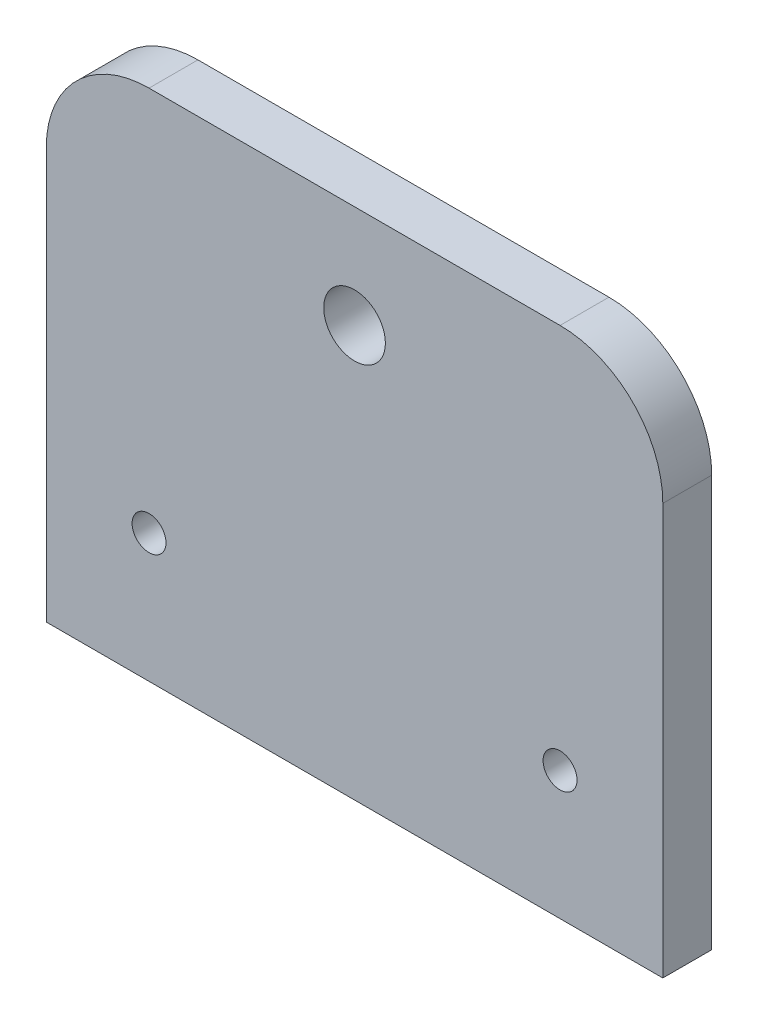
SolidWorks part; units mm, degrees
ref_plane "Front Plane" through (0, 0, 0) normal (0, 0, 1) x (1, 0, 0)
ref_plane "Top Plane" through (0, 0, 0) normal (0, 1, 0) x (1, 0, 0)
ref_plane "Right Plane" through (0, 0, 0) normal (1, 0, 0) x (0, 0, -1)
sketch "Sketch1" plane through (0, 0, 0) normal (0, 0, 1) x (1, 0, 0)
  line L1 (0, 0) -> (60, 0)
  line L2 (0, 0) -> (0, 50)
  line L3 (0, 50) -> (60, 50)
  line L4 (60, 0) -> (60, 50)
  dimension "D1" = 50
  dimension "D2" = 60
extrude "Boss-Extrude1" add sketch "Sketch1" along normal blind 4.76
sketch "Sketch2" plane through (0, 0, 4.76) normal (0, 0, 1) x (1, 0, 0)
  line L0 (0, 12.5) -> (60, 12.5) construction
  line L1 (0, 50) -> (0, 0) construction
  line L2 (60, 0) -> (60, 50) construction
  line L3 (0, 0) -> (60, 0) construction
  line L4 (30, 50) -> (30, 0) construction
  line L5 (60, 50) -> (0, 50) construction
  circle A0 centre (10, 12.5) radius 1.65
  circle A2 centre (50, 12.5) radius 1.65
  circle A3 centre (30, 40) radius 3
  dimension "D2" = 3.3
  dimension "D4" = 6
  dimension "D1" = 12.5
  dimension "D3" = 20
  dimension "D5" = 10
extrude "Cut-Extrude1" cut sketch "Sketch2" against normal through all
fillet "Fillet1" radius 10 2 edges at (60, 50, 2.38) (0, 50, 2.38)
equation "\"Screw Size\"= 6mm"
equation "\"D4@Sketch2\"= \"Screw Size\""
